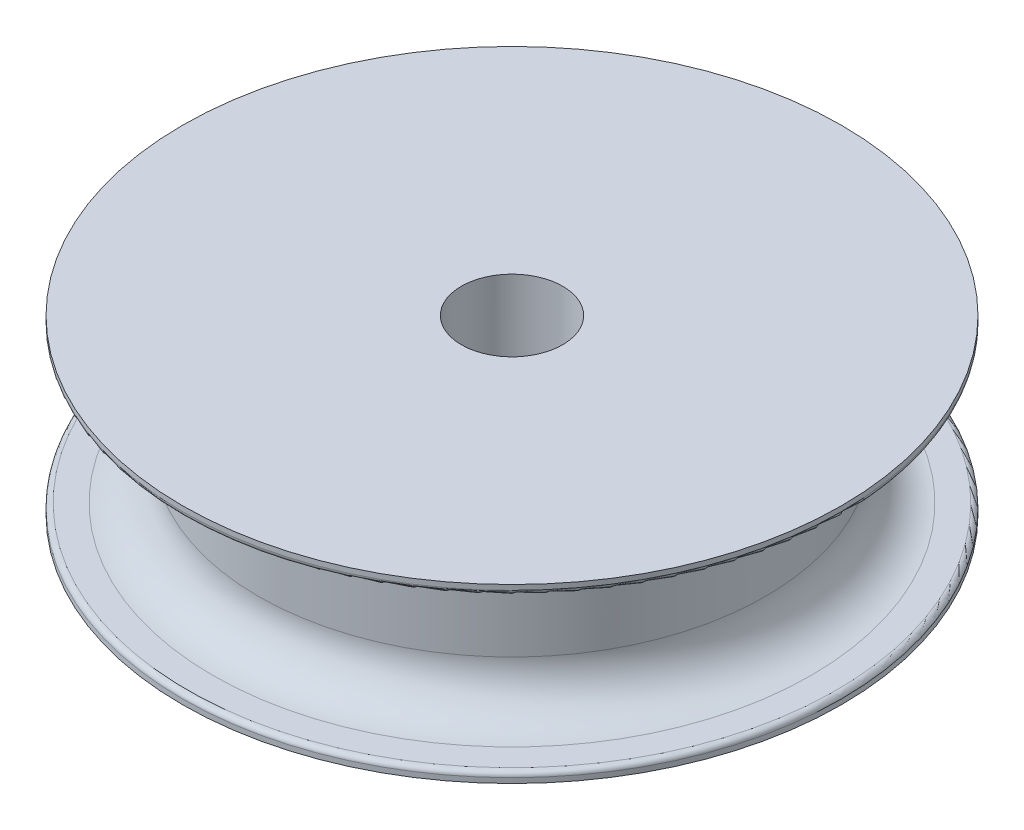
SolidWorks part; units mm, degrees
ref_plane "Front Plane" through (0, 0, 0) normal (0, 0, 1) x (1, 0, 0)
ref_plane "Top Plane" through (0, 0, 0) normal (0, 1, 0) x (1, 0, 0)
ref_plane "Right Plane" through (0, 0, 0) normal (1, 0, 0) x (0, 0, -1)
sketch "Sketch1" plane through (0, 0, 0) normal (0, 1, 0) x (1, 0, 0)
  circle A0 centre (0, 0) radius 50
  dimension "D1" = 100
extrude "Boss-Extrude1" add sketch "Sketch1" along normal blind 15 and the other way blind 15
sketch "Sketch2" plane through (0, -15, 0) normal (0, -1, 0) x (1, 0, 0)
  circle A0 centre (0, 0) radius 65
  dimension "D1" = 130
extrude "Boss-Extrude2" add sketch "Sketch2" along normal blind 2
sketch "Sketch3" plane through (0, 15, 0) normal (0, 1, 0) x (1, 0, 0)
  circle A0 centre (0, 0) radius 65 construction
  circle A1 centre (0, 0) radius 65
extrude "Boss-Extrude3" add sketch "Sketch3" along normal blind 2
fillet "Fillet1" radius 9 1 edges at (0, -15, -50)
fillet "Fillet2" radius 1 1 edges at (0, -15, -65)
fillet "Fillet3" radius 1 1 edges at (0, 15, 65)
fillet "Fillet4" radius 9 1 edges at (0, 15, 50)
sketch "Sketch4" plane through (0, 17, 0) normal (0, 1, 0) x (1, 0, 0)
  circle A0 centre (0, 0) radius 10
  dimension "D1" = 20
extrude "Cut-Extrude1" cut sketch "Sketch4" against normal up to next
